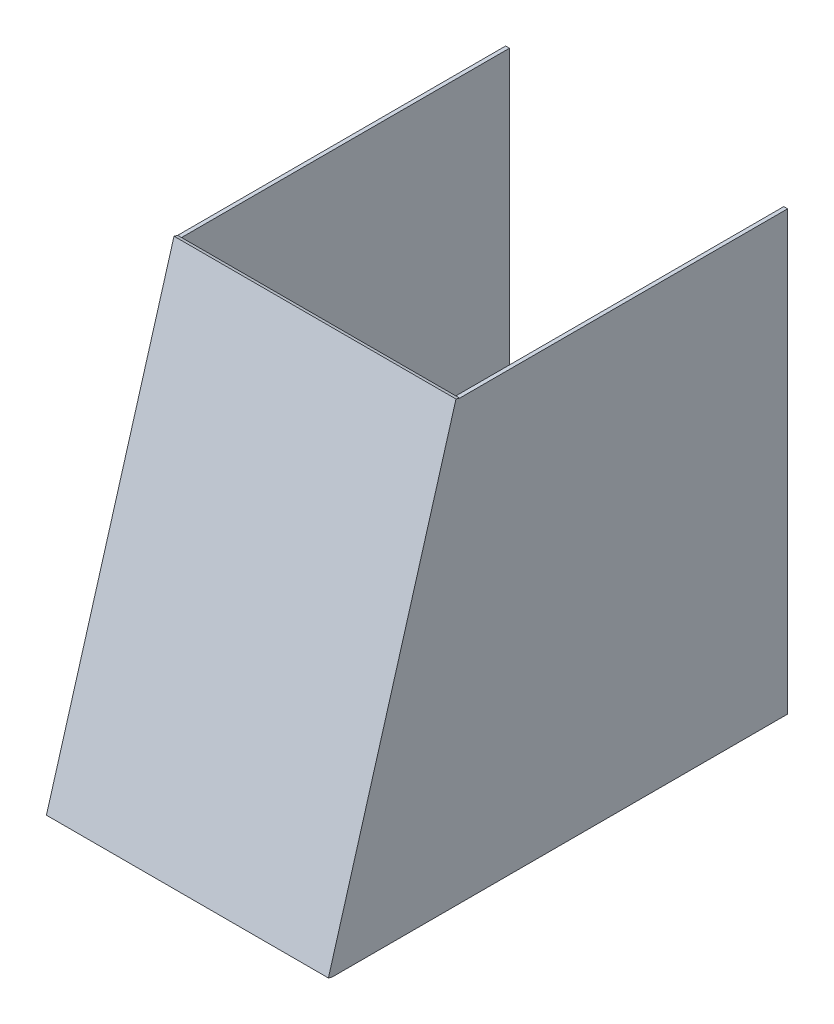
SolidWorks part; units mm, degrees
ref_plane "Front Plane" through (0, 0, 0) normal (0, 0, 1) x (1, 0, 0)
ref_plane "Top Plane" through (0, 0, 0) normal (0, 1, 0) x (1, 0, 0)
ref_plane "Right Plane" through (0, 0, 0) normal (1, 0, 0) x (0, 0, -1)
sketch "Sketch1" plane through (107.5, 0, 0) normal (1, 0, 0) x (0, 0, -1)
  line L0 (125.5, 330) -> (-131.5, 330)
  line L1 (-131.5, 330) -> (-231.5, -13)
  line L2 (-231.5, -13) -> (125.5, -13)
  line L3 (125.5, -13) -> (125.5, 330)
  dimension "D1" = 357
  dimension "D2" = 257
extrude "Boss-Extrude1" add sketch "Sketch1" along normal blind 3
mirror "Mirror2" about plane through (0, 0, 0) normal (1, 0, 0) of bodies 101
sketch "Sketch2" plane through (0, 61.1869, 209.8712) normal (0, 0.2799, 0.96) x (1, 0, 0)
  line L0 (-110.5, 280.0045) -> (110.5, 280.0045)
  line L1 (110.5, 280.0045) -> (110.5, -77.2755)
  line L2 (110.5, -77.2755) -> (-110.5, -77.2755)
  line L3 (-110.5, -77.2755) -> (-110.5, 280.0045)
extrude "Boss-Extrude2" add sketch "Sketch2" along normal blind 3
